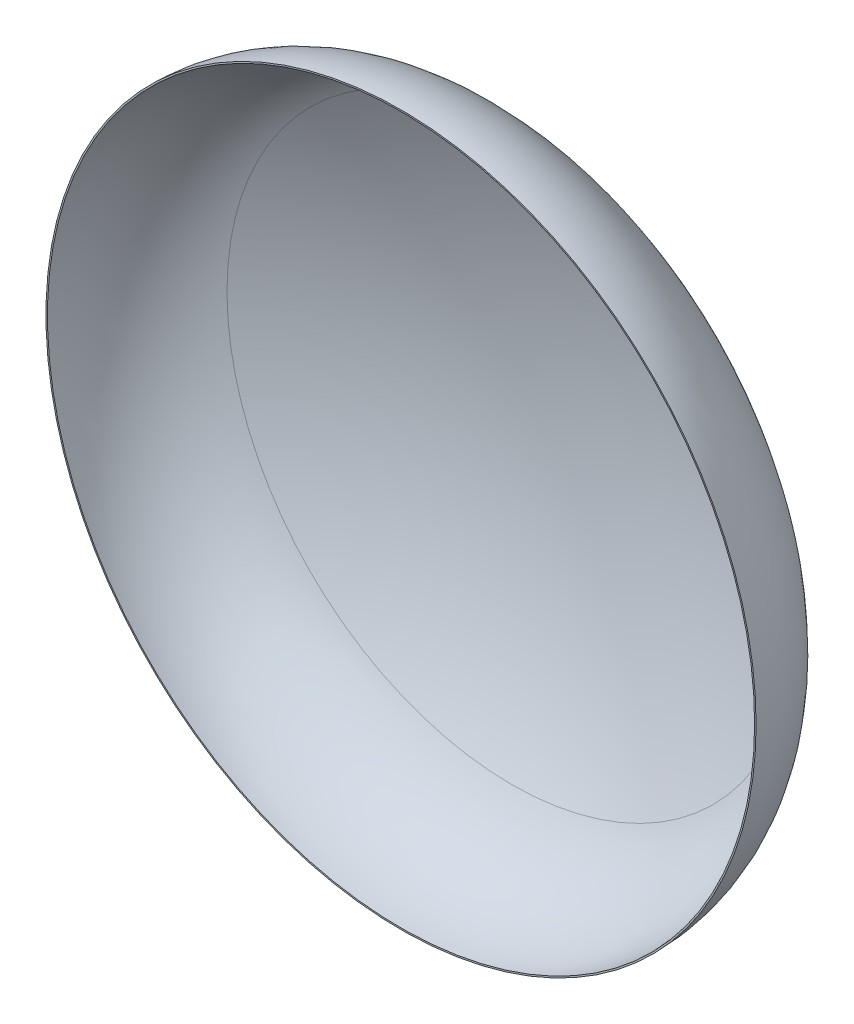
SolidWorks part; units mm, degrees
ref_plane "Front Plane" through (0, 0, 0) normal (0, 0, 1) x (1, 0, 0)
ref_plane "Top Plane" through (0, 0, 0) normal (0, 1, 0) x (1, 0, 0)
ref_plane "Right Plane" through (0, 0, 0) normal (1, 0, 0) x (0, 0, -1)
sketch "Sketch1" plane through (0, 0, 0) normal (1, 0, 0) x (0, 0, -1)
  line L0 (7.0957, 24.0145) -> (7.0957, 23.9145)
  line L7 (7.0957, -24.1855) -> (7.0957, -24.0855)
  arc A0 (19.0957, 0) -> (14.5881, 19.2635) centre (-24.3203, 0) ccw
  arc A2 (14.5881, 19.2635) -> (7.0957, 23.9145) centre (7.0957, 15.5541) ccw
  arc A4 (19.1957, 0) -> (14.6777, 19.3079) centre (-24.3203, 0) ccw
  arc A5 (14.6777, 19.3079) -> (7.0957, 24.0145) centre (7.0957, 15.5541) ccw
  arc A7 (14.4351, -19.5695) -> (14.5881, 19.2635) centre (-24.3203, 0) ccw construction
  arc A8 (14.5244, -19.6146) -> (14.6777, 19.3079) centre (-24.3203, 0) ccw construction
  arc A9 (14.4351, -19.5695) -> (7.0957, -24.0855) centre (7.0957, -15.8635) cw construction
  arc A10 (14.5244, -19.6146) -> (7.0957, -24.1855) centre (7.0957, -15.8635) cw construction
  dimension "D1" = 43.416
  dimension "D2" = 8.3604
  dimension "D6" = 19.3079
  dimension "D3" = 48
  dimension "D4" = 0.1
  dimension "D5" = 7.0957
revolve "Revolve-Thin2" add sketch "Sketch1" angle 360 about L0
scale "Scale1" scale about centroid uniform scaling yes scale factor 25.4
